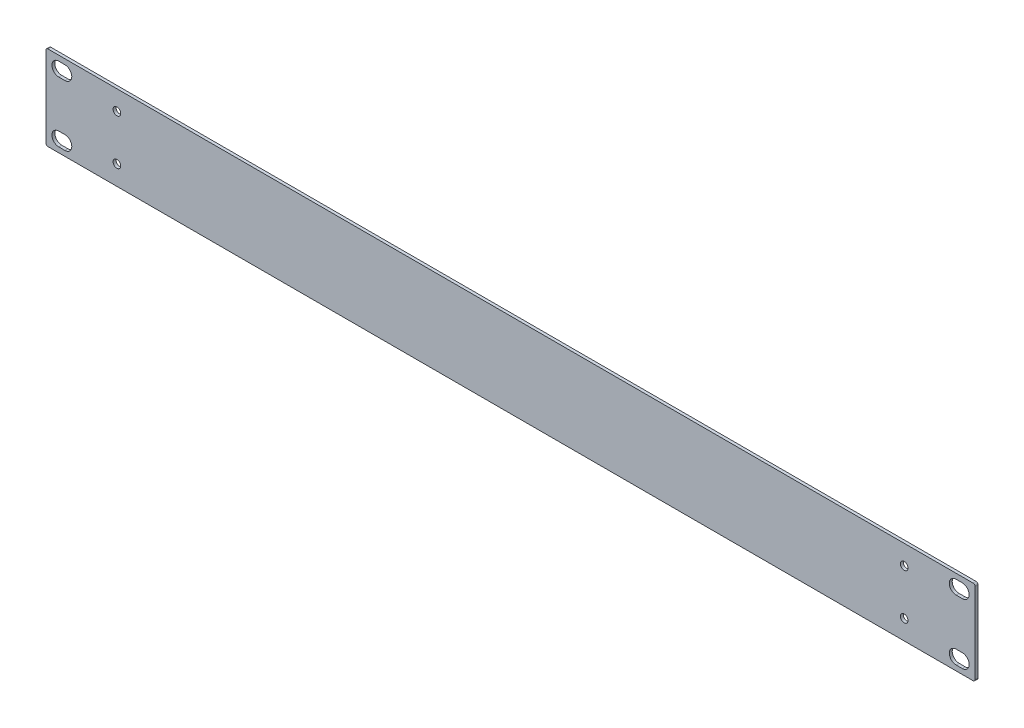
SolidWorks part; units mm, degrees
note: The reader was unsure of these and kept them because the rebuilt part matched: thickness of "Base-Flange1", "Sheet-Metal3", "Sheet-Metal4", "Sheet-Metal5".
ref_plane "Front Plane" through (0, 0, 0) normal (0, 0, 1) x (1, 0, 0)
ref_plane "Top Plane" through (0, 0, 0) normal (0, 1, 0) x (1, 0, 0)
ref_plane "Right Plane" through (0, 0, 0) normal (1, 0, 0) x (0, 0, -1)
sketch "Sketch1" plane through (0, 0, 0) normal (0, 0, 1) x (1, 0, 0)
  line L0 (241.3, 42.926) -> (241.3, 1.016)
  line L1 (240.284, 43.942) -> (-240.284, 43.942)
  line L2 (240.284, 0) -> (-240.284, 0)
  line L3 (-241.3, 42.926) -> (-241.3, 1.016)
  line L4 (241.3, 43.942) -> (-241.3, 0) construction
  line L5 (241.3, 0) -> (-241.3, 43.942) construction
  arc A0 (-240.284, 0) -> (-241.3, 1.016) centre (-240.284, 1.016) cw
  arc A1 (241.3, 1.016) -> (240.284, 0) centre (240.284, 1.016) cw
  arc A2 (240.284, 43.942) -> (241.3, 42.926) centre (240.284, 42.926) cw
  arc A3 (-240.284, 43.942) -> (-241.3, 42.926) centre (-240.284, 42.926) ccw
  point P1 (0, 21.971)
  point P18 (0, 0)
  dimension "D3" = 1.016
  dimension "D1" = 482.6
  dimension "D2" = 43.942
base flange "Base-Flange1" sketch "Sketch1" thickness 1.524 reverse thickness direction no parameters "D1"=1.905
sketch "Sketch2" plane through (0, 0, 0) normal (0, 0, 1) x (1, 0, 0)
  line L0 (-234.6706, 6.2484) -> (-231.4702, 6.2484) construction
  line L1 (-234.6706, 9.8044) -> (-231.4702, 9.8044)
  line L2 (-234.6706, 2.6924) -> (-231.4702, 2.6924)
  line L3 (-241.3, 42.926) -> (-241.3, 1.016) construction
  line L4 (240.284, 43.942) -> (-240.284, 43.942) construction
  line L5 (-241.3, 21.971) -> (241.3, 21.971) construction
  line L6 (241.3, 1.016) -> (241.3, 42.926) construction
  line L7 (0, 0) -> (0, 43.942) construction
  line L8 (-234.6706, 37.6936) -> (-231.4702, 37.6936) construction
  line L9 (-234.6706, 34.1376) -> (-231.4702, 34.1376)
  line L10 (-234.6706, 41.2496) -> (-231.4702, 41.2496)
  line L11 (234.6706, 6.2484) -> (231.4702, 6.2484) construction
  line L12 (234.6706, 9.8044) -> (231.4702, 9.8044)
  line L13 (234.6706, 2.6924) -> (231.4702, 2.6924)
  line L14 (234.6706, 37.6936) -> (231.4702, 37.6936) construction
  line L15 (234.6706, 34.1376) -> (231.4702, 34.1376)
  line L16 (234.6706, 41.2496) -> (231.4702, 41.2496)
  arc A0 (-234.6706, 9.8044) -> (-234.6706, 2.6924) centre (-234.6706, 6.2484) ccw
  arc A1 (-231.4702, 2.6924) -> (-231.4702, 9.8044) centre (-231.4702, 6.2484) ccw
  arc A2 (-234.6706, 34.1376) -> (-234.6706, 41.2496) centre (-234.6706, 37.6936) cw
  arc A3 (-231.4702, 41.2496) -> (-231.4702, 34.1376) centre (-231.4702, 37.6936) cw
  arc A4 (234.6706, 9.8044) -> (234.6706, 2.6924) centre (234.6706, 6.2484) cw
  arc A5 (231.4702, 2.6924) -> (231.4702, 9.8044) centre (231.4702, 6.2484) cw
  arc A6 (234.6706, 34.1376) -> (234.6706, 41.2496) centre (234.6706, 37.6936) ccw
  arc A7 (231.4702, 41.2496) -> (231.4702, 34.1376) centre (231.4702, 37.6936) ccw
  point P2 (-233.0704, 6.2484)
  point P7 (-227.9142, 6.2484)
  point P21 (-233.0704, 37.6936)
  point P28 (233.0704, 6.2484)
  point P35 (233.0704, 37.6936)
  dimension "D5" = 3.556
  dimension "D1" = 7.112
  dimension "D2" = 3.2004
  dimension "D3" = 13.3858
  dimension "D4" = 37.6936
extrude "Cut-Extrude-Mounting" cut sketch "Sketch2" against normal through all normal cut yes
sketch "Sketch5" plane through (0, 0, 0) normal (0, 0, 1) x (1, 0, 0)
  line L0 (-241.3, 21.971) -> (241.3, 21.971) construction
  line L1 (-241.3, 42.926) -> (-241.3, 1.016) construction
  line L2 (241.3, 1.016) -> (241.3, 42.926) construction
  line L3 (0, 0) -> (0, 43.942) construction
  line L4 (240.284, 43.942) -> (-240.284, 43.942) construction
  circle A0 centre (-204.47, 33.782) radius 2
  circle A1 centre (-204.47, 10.16) radius 2
  circle A2 centre (204.47, 10.16) radius 2
  circle A3 centre (204.47, 33.782) radius 2
  dimension "D1" = 4
  dimension "D2" = 36.83
  dimension "D3" = 10.16
extrude "Cut-Extrude-Cover" cut sketch "Sketch5" against normal blind 2.54
sketch "Bend-Lines4" [suppressed] plane through (0, 0, 0) normal (0, 1, 0) x (-1, 0, 0)
sketch "Bounding-Box4" [suppressed] plane through (0, 0, 0) normal (0, 1, 0) x (-1, 0, 0)
sheet metal parameters "Sheet-Metal3" thickness 1.524 parameters "D1"=1.905, "D7"=1.2192
flat pattern "Flat-Pattern3" [suppressed]
sketch "Bend-Lines5" plane through (0, 0, 0) normal (0, 1, 0) x (-1, 0, 0)
sketch3d "Bounding-Box5" [suppressed]
  line L0 (-1.016, -1.016, 0) -> (481.584, -1.016, 0) construction
  line L1 (-1.016, 42.926, 0) -> (481.584, 42.926, 0) construction
  line L2 (-1.016, -1.016, 0) -> (-1.016, 42.926, 0) construction
  line L3 (481.584, -1.016, 0) -> (481.584, 42.926, 0) construction
sheet metal parameters "Sheet-Metal4" thickness 1.524 parameters "D1"=1.905, "D7"=1.2192
flat pattern "Flat-Pattern3"
sketch "Bend-Lines5" plane through (0, 0, 0) normal (0, 1, 0) x (-1, 0, 0)
sketch3d "Bounding-Box5" [suppressed]
  line L0 (-1.016, -1.016, 0) -> (481.584, -1.016, 0) construction
  line L1 (-1.016, 42.926, 0) -> (481.584, 42.926, 0) construction
  line L2 (-1.016, -1.016, 0) -> (-1.016, 42.926, 0) construction
  line L3 (481.584, -1.016, 0) -> (481.584, 42.926, 0) construction
sheet metal parameters "Sheet-Metal5" thickness 1.524 parameters "D1"=1.905, "D7"=1.2192
flat pattern "Flat-Pattern3"
sketch "Bend-Lines5" plane through (0, 0, 0) normal (0, 1, 0) x (-1, 0, 0)
sketch3d "Bounding-Box5" [suppressed]
  line L0 (-1.016, -1.016, 0) -> (481.584, -1.016, 0) construction
  line L1 (-1.016, 42.926, 0) -> (481.584, 42.926, 0) construction
  line L2 (-1.016, -1.016, 0) -> (-1.016, 42.926, 0) construction
  line L3 (481.584, -1.016, 0) -> (481.584, 42.926, 0) construction
